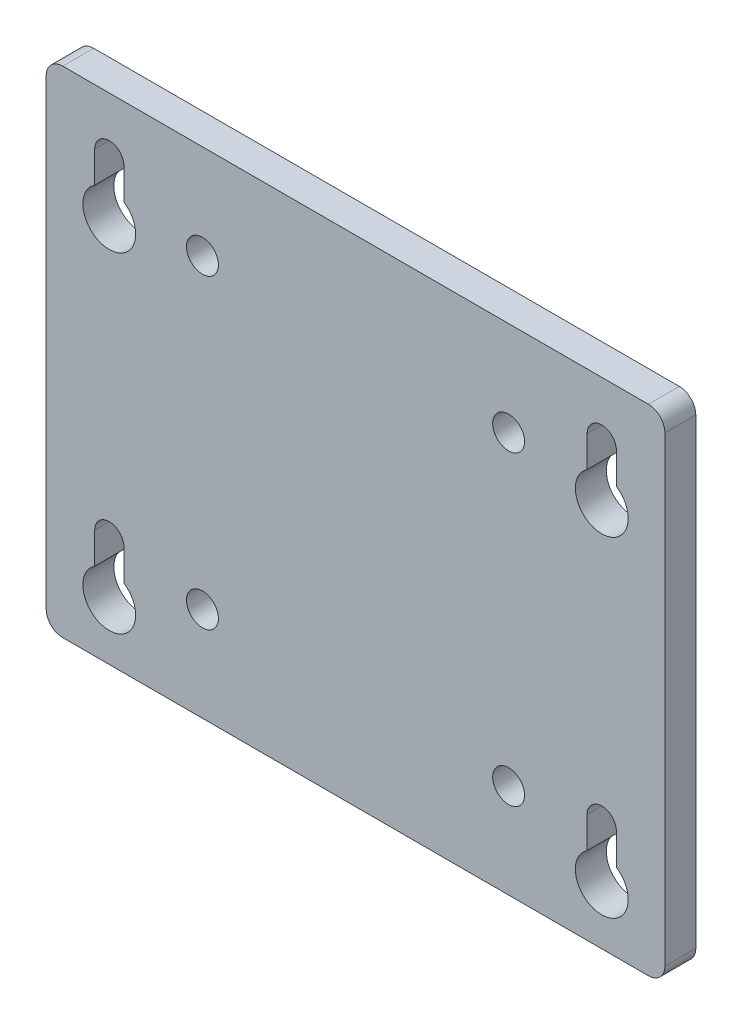
SolidWorks part; units mm, degrees
ref_plane "Front Plane" through (0, 0, 0) normal (0, 0, 1) x (1, 0, 0)
ref_plane "Top Plane" through (0, 0, 0) normal (0, 1, 0) x (1, 0, 0)
ref_plane "Right Plane" through (0, 0, 0) normal (1, 0, 0) x (0, 0, -1)
sketch "Sketch1" plane through (0, 0, 0) normal (0, 0, 1) x (1, 0, 0)
  line L1 (47.625, -38.1) -> (-47.625, -38.1)
  line L2 (47.625, -38.1) -> (47.625, 38.1)
  line L3 (47.625, 38.1) -> (-47.625, 38.1)
  line L4 (-47.625, -38.1) -> (-47.625, 38.1)
  line L5 (47.625, -38.1) -> (-47.625, 38.1) construction
  line L6 (47.625, 38.1) -> (-47.625, -38.1) construction
  point P0 (0, 0)
  dimension "D1" = 76.2
  dimension "D2" = 95.25
extrude "Boss-Extrude1" add sketch "Sketch1" along normal blind 4.7625
hole_wizard "#8 Clearance Hole1" positions "Sketch3" profile "Sketch2" hole size "#8" standard "ANSI Inch" end condition through all
sketch "Sketch3" plane through (0, 0, 4.7625) normal (0, 0, 1) x (1, 0, 0)
  point P0 (23.57, 23.57)
  point P3 (-23.57, 23.57)
  point P6 (-23.57, -23.57)
  point P9 (23.57, -23.57)
sketch "Sketch2" plane through (23.57, 23.57, 4.7625) normal (1, 0, 0) x (0, -1, 0)
  line L0 (0, 0) -> (0, 4.7625)
  line L1 (0, 4.7625) -> (2.4574, 4.7625)
  line L2 (2.4574, 4.7625) -> (2.4574, 0)
  line L5 (2.4574, 0) -> (0, 0)
  line L11 (0, -6.35) -> (0, 107.95) construction
  dimension "Thru Hole Dia." = 4.9149
  dimension "Thru Hole Depth" = 4.7625
fillet "Fillet1" radius 2.54 4 edges at (47.625, -38.1, 2.3813) (-47.625, -38.1, 2.3813) (-47.625, 38.1, 2.3813) (47.625, 38.1, 2.3813)
hole_wizard "#8 Clearance Slot1" positions "Sketch5" profile "Sketch4" size "#8" standard "ANSI Inch" slot yes end condition through all
sketch "Sketch5" plane through (0, 0, 0) normal (0, 0, -1) x (-1, 0, 0)
  line L0 (-37.9125, 31.75) -> (-37.9125, 19.05) construction
  line L1 (-28.2, 25.4) -> (-47.625, 25.4) construction
  line L3 (-47.625, -35.56) -> (-47.625, 35.56) construction
  line L5 (-45.085, 38.1) -> (45.085, 38.1) construction
  line L6 (0, 38.1) -> (0, -38.1) construction
  line L7 (45.085, -38.1) -> (-45.085, -38.1) construction
  line L9 (47.625, 0) -> (-47.625, 0) construction
  line L10 (47.625, 35.56) -> (47.625, -35.56) construction
  line L12 (-28.2, -25.4) -> (-47.625, -25.4) construction
  line L13 (-37.9125, -31.75) -> (-37.9125, -19.05) construction
  line L14 (37.9125, -31.75) -> (37.9125, -19.05) construction
  line L15 (28.2, -25.4) -> (47.625, -25.4) construction
  line L16 (28.2, 25.4) -> (47.625, 25.4) construction
  line L17 (37.9125, 31.75) -> (37.9125, 19.05) construction
  line L18 (-28.2, -23.755) -> (-28.2, 38.1) construction
  point P0 (-37.9125, 25.4)
  point P36 (-37.9125, -25.4)
  point P45 (37.9125, -25.4)
  point P46 (37.9125, 25.4)
  dimension "D1" = 12.7
  dimension "D2" = 6.35
sketch "Sketch4" plane through (37.9125, 25.4, 0) normal (1, 0, 0) x (0, 1, 0)
  line L0 (0, 0) -> (0, 4.7625)
  line L1 (0, 4.7625) -> (2.2479, 4.7625)
  line L2 (2.2479, 4.7625) -> (2.2479, 0)
  line L5 (2.2479, 0) -> (0, 0)
  line L11 (0, -6.35) -> (0, 107.95) construction
  dimension "Thru Hole Dia." = 4.4958
  dimension "Thru Hole Depth" = 4.7625
sketch "Sketch6" plane through (0, 0, 0) normal (0, 0, -1) x (-1, 0, 0)
  line L0 (0, 38.1) -> (0, -38.1) construction
  line L1 (-45.085, 38.1) -> (45.085, 38.1) construction
  line L2 (45.085, -38.1) -> (-45.085, -38.1) construction
  circle A0 centre (-37.9125, 21.2979) radius 4.064
  circle A1 centre (-37.9125, -29.5021) radius 4.064
  circle A2 centre (37.9125, -29.5021) radius 4.064
  circle A3 centre (37.9125, 21.2979) radius 4.064
  dimension "D1" = 8.128
  dimension "D2" = 8.128
extrude "Cut-Extrude1" cut sketch "Sketch6" against normal through all
